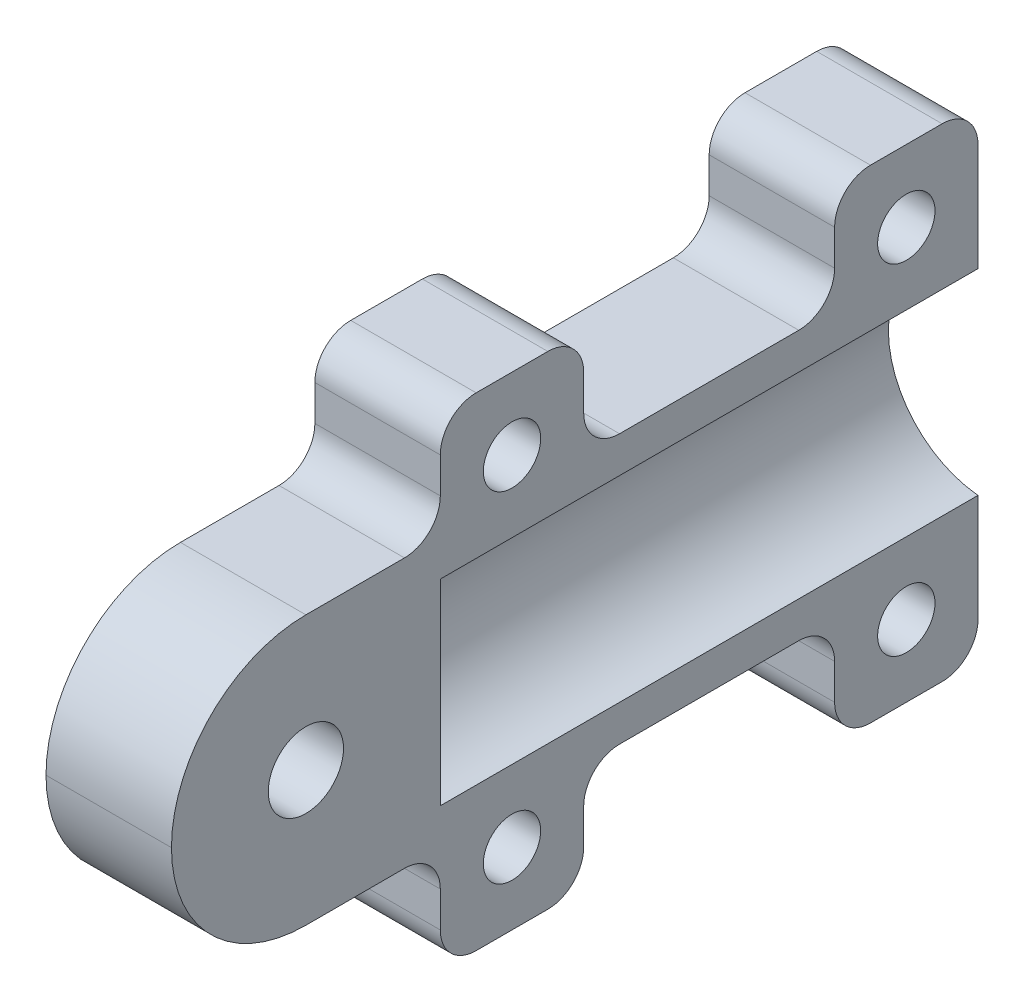
SolidWorks part; units mm, degrees
ref_plane "正面" through (0, 0, 0) normal (0, 0, 1) x (1, 0, 0)
ref_plane "平面" through (0, 0, 0) normal (0, 1, 0) x (1, 0, 0)
ref_plane "右側面" through (0, 0, 0) normal (1, 0, 0) x (0, 0, -1)
sketch "ｽｹｯﾁ1" plane through (0, 0, 0) normal (0, 0, 1) x (1, 0, 0)
  line L1 (-7.5, -7.5) -> (7.5, -7.5)
  line L2 (-7.5, -7.5) -> (-7.5, 7.5)
  line L3 (-7.5, 7.5) -> (7.5, 7.5)
  line L4 (7.5, -7.5) -> (7.5, 7.5)
  line L5 (-7.5, -7.5) -> (7.5, 7.5) construction
  line L6 (-7.5, 7.5) -> (7.5, -7.5) construction
  circle A0 centre (0, 0) radius 5.5
  dimension "D1" = 11
  dimension "D3" = 15
  dimension "D4" = 15
extrude "ﾎﾞｽ - 押し出し1" add sketch "ｽｹｯﾁ1" along normal blind 45
sketch "ｽｹｯﾁ5" plane through (0, 0, 45) normal (0, 0, 1) x (1, 0, 0)
  line L1 (7.5, -7.5) -> (-7.5, -7.5)
  line L2 (7.5, -7.5) -> (7.5, 7.5)
  line L3 (7.5, 7.5) -> (-7.5, 7.5)
  line L4 (-7.5, -7.5) -> (-7.5, 7.5)
  line L5 (7.5, -7.5) -> (-7.5, 7.5) construction
  line L6 (7.5, 7.5) -> (-7.5, -7.5) construction
  point P0 (0, 0)
extrude "ﾎﾞｽ - 押し出し3" add sketch "ｽｹｯﾁ5" against normal blind 15
fillet "ﾌｨﾚｯﾄ2" radius 7.5 2 edges at (0, -7.5, 45) (0, 7.5, 45)
sketch "ｽｹｯﾁ6" plane through (7.5, 0, 0) normal (1, 0, 0) x (0, 0, -1)
  circle A0 centre (-37.5, 0) radius 2.1
  dimension "D1" = 4.2
extrude "ｶｯﾄ - 押し出し1" cut sketch "ｽｹｯﾁ6" against normal through all
sketch "ｽｹｯﾁ7" plane through (7.5, 0, 0) normal (1, 0, 0) x (0, 0, -1)
  line L10 (-37.5, -9.5) -> (2, -9.5)
  line L11 (2, -9.5) -> (2, 9.5)
  line L12 (2, 9.5) -> (-37.5, 9.5)
  line L13 (-37.5, -9.5) -> (2, -9.5)
  line L14 (2, -9.5) -> (2, 9.5)
  line L15 (2, 9.5) -> (-37.5, 9.5)
  arc A6 (-37.5, 9.5) -> (-47, 0) centre (-37.5, 0) ccw
  arc A7 (-47, 0) -> (-37.5, -9.5) centre (-37.5, 0) ccw
  arc A8 (-37.5, 9.5) -> (-47, 0) centre (-37.5, 0) ccw
  arc A9 (-47, 0) -> (-37.5, -9.5) centre (-37.5, 0) ccw
  dimension "D1" = 2
extrude "ｶｯﾄ - 押し出し2" cut sketch "ｽｹｯﾁ7" against normal blind 8
sketch "ｽｹｯﾁ9" plane through (-0.5, 0, 0) normal (1, 0, 0) x (0, 0, -1)
  line L0 (-30, -5.4772) -> (0, -5.4772) construction
  line L1 (0, -5.4772) -> (-8, -5.4772)
  line L2 (0, -5.4772) -> (0, -13.4772)
  line L3 (0, -13.4772) -> (-8, -13.4772)
  line L4 (-8, -5.4772) -> (-8, -13.4772)
  line L5 (-30, 5.4772) -> (-22, 5.4772)
  line L6 (-30, 5.4772) -> (-30, 13.4772)
  line L7 (-30, 13.4772) -> (-22, 13.4772)
  line L8 (-22, 5.4772) -> (-22, 13.4772)
  line L9 (0, 5.4772) -> (-8, 5.4772)
  line L10 (0, 5.4772) -> (0, 13.4772)
  line L11 (0, 13.4772) -> (-8, 13.4772)
  line L12 (-8, 5.4772) -> (-8, 13.4772)
  line L13 (-22, -5.4772) -> (-30, -5.4772)
  line L14 (-22, -5.4772) -> (-22, -13.4772)
  line L15 (-22, -13.4772) -> (-30, -13.4772)
  line L16 (-30, -5.4772) -> (-30, -13.4772)
  circle A0 centre (-4, -9.4772) radius 1.6
  circle A1 centre (-26, 9.4772) radius 1.6
  circle A2 centre (-26, -9.4772) radius 1.6
  circle A3 centre (-4, 9.4772) radius 1.6
  dimension "D7" = 4
  dimension "D8" = 4
  dimension "D9" = 3.2
  dimension "D10" = 4
  dimension "D11" = 4
  dimension "D12" = 3.2
  dimension "D13" = 3.2
  dimension "D14" = 4
  dimension "D16" = 4
  dimension "D18" = 3.2
  dimension "D1" = 8
  dimension "D2" = 8
  dimension "D3" = 8
  dimension "D4" = 8
  dimension "D5" = 8
  dimension "D6" = 8
  dimension "D15" = 4
  dimension "D17" = 4
extrude "ﾎﾞｽ - 押し出し4" add sketch "ｽｹｯﾁ9" against normal blind 7
fillet "ﾌｨﾚｯﾄ3" radius 2 14 edges at (-4, 7.5, 30) (-4, 13.4772, 30) (-4, 13.4772, 22) (-4, 7.5, 22) (-4, 7.5, 8) (-4, 13.4772, 8) (-4, 13.4772, 0) (-4, -13.4772, 0) (-4, -13.4772, 8) (-4, -7.5, 8) (-4, -7.5, 22) (-4, -13.4772, 22) (-4, -7.5, 30) (-4, -13.4772, 30)
sketch "ｽｹｯﾁ11" plane through (-7.5, 0, 0) normal (-1, 0, 0) x (0, 0, 1)
  circle A0 centre (4, 9.4772) radius 3.2
  circle A1 centre (26, 9.4772) radius 3.2
  circle A2 centre (26, -9.4772) radius 3.2
  circle A3 centre (4, -9.4772) radius 3.2
  dimension "D1" = 6.4
  dimension "D2" = 6.4
  dimension "D3" = 6.4
  dimension "D4" = 6.4
extrude "ｶｯﾄ - 押し出し3" cut sketch "ｽｹｯﾁ11" against normal blind 3.75
